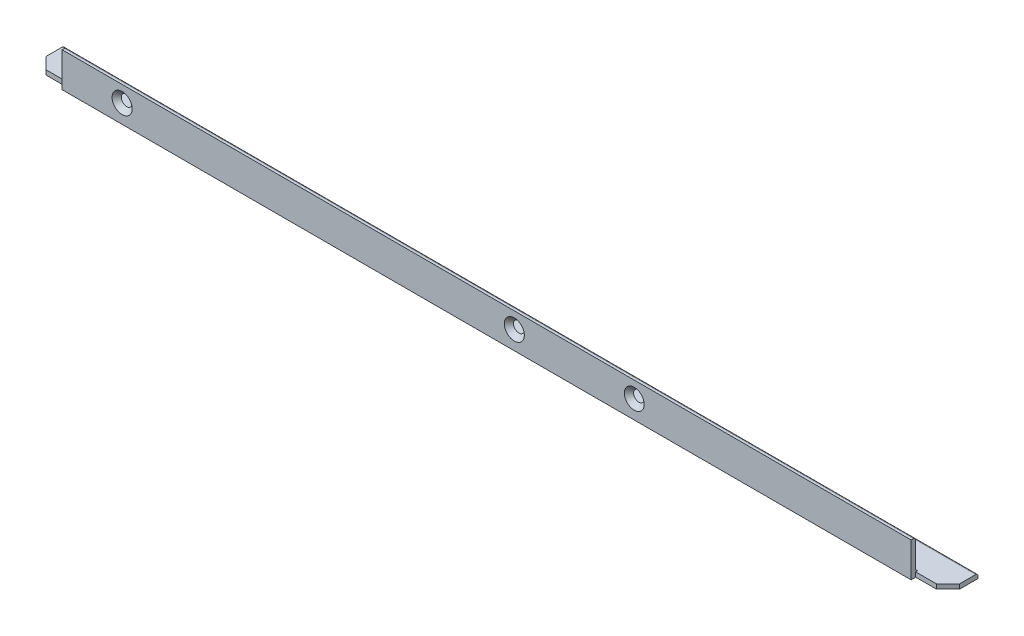
SolidWorks part; units mm, degrees
material "1060 Сплав"
ref_plane "Front" through (0, 0, 0) normal (0, 0, 1) x (1, 0, 0)
ref_plane "Top" through (0, 0, 0) normal (0, 1, 0) x (1, 0, 0)
ref_plane "Right" through (0, 0, 0) normal (1, 0, 0) x (0, 0, -1)
sketch "Эскиз1" plane through (0, 0, 0) normal (1, 0, 0) x (0, 0, -1)
  line L0 (0, 0) -> (0, 15)
  line L1 (0, 0) -> (15, 0)
  line L2 (0, 15) -> (1, 15)
  line L3 (2, 14) -> (2, 3)
  line L4 (3, 2) -> (14, 2)
  line L5 (15, 1) -> (15, 0)
  arc A0 (14, 2) -> (15, 1) centre (14, 1) cw
  arc A1 (1, 15) -> (2, 14) centre (1, 14) cw
  arc A2 (2, 3) -> (3, 2) centre (3, 3) ccw
  point P9 (15, 2)
  point P12 (2, 15)
  dimension "D5" = 1
  dimension "D1" = 15
  dimension "D2" = 15
  dimension "D3" = 2
  dimension "D4" = 2
extrude "Бобышка-Вытянуть1" add sketch "Эскиз1" along normal blind 396
sketch "Эскиз4" plane through (0, 0, 0) normal (0, -1, 0) x (1, 0, 0)
  line L0 (396, -15) -> (0, -15) construction
  line L1 (0, 0) -> (0, -15) construction
  line L2 (396, 0) -> (396, -15) construction
  circle A0 centre (371, -8) radius 2.25
  circle A1 centre (198, -8) radius 2.25
  circle A2 centre (25, -8) radius 2.25
  dimension "D1" = 4.5
  dimension "D2" = 7
  dimension "D3" = 25
  dimension "D4" = 4.5
  dimension "D5" = 25
  dimension "D6" = 7
  dimension "D7" = 173
  dimension "D8" = 4.5
extrude "Вырез-Вытянуть3" cut sketch "Эскиз4" against normal blind 2
chamfer "Фаска1" distance 2.05 angle 45 3 edges at (25, 0, -10.25) (371, 0, -10.25) (198, 0, -10.25)
sketch "Эскиз5" [suppressed] plane through (0, 2, 0) normal (0, 1, 0) x (1, 0, 0)
  line L0 (432, 14) -> (432, 3) construction
  line L1 (432, 15) -> (0, 15) construction
  line L2 (0, 14) -> (0, 3) construction
  circle A0 centre (392, 8) radius 2.3
  circle A1 centre (40, 8) radius 2.3
  dimension "D1" = 4.6
  dimension "D2" = 40
  dimension "D3" = 7
  dimension "D4" = 4.6
  dimension "D5" = 7
  dimension "D6" = 40
extrude "Вырез-Вытянуть4" [suppressed] cut sketch "Эскиз5" against normal through all
chamfer "Фаска3" [suppressed] distance 2.05 angle 45
sketch "Эскиз6" plane through (396, 0, 0) normal (1, 0, 0) x (0, 0, -1)
  line L0 (0, 0) -> (15, 0) construction
  line L1 (0, 15) -> (2, 15)
  line L2 (0, 15) -> (0, 0)
  line L3 (0, 0) -> (2, 0)
  line L4 (2, 0) -> (2, 2)
  line L5 (2, 2) -> (3, 2)
  line L6 (3, 2) -> (3, 15)
  line L7 (3, 15) -> (2, 15)
extrude "Вырез-Вытянуть5" cut sketch "Эскиз6" against normal blind 14
sketch "Эскиз7" plane through (0, 0, 0) normal (-1, 0, 0) x (0, 0, 1)
  line L0 (0, 0) -> (-15, 0) construction
  line L1 (0, 15) -> (-2, 15)
  line L2 (0, 15) -> (0, 0)
  line L3 (0, 0) -> (-2, 0)
  line L4 (-3, 2) -> (-2, 2)
  line L5 (-2, 2) -> (-2, 0)
  line L6 (-3, 2) -> (-3, 15)
  line L7 (-3, 15) -> (-2, 15)
extrude "Вырез-Вытянуть6" cut sketch "Эскиз7" against normal blind 14
sketch "Эскиз9" plane through (0, 2, 0) normal (0, 1, 0) x (1, 0, 0)
  line L0 (0, 2) -> (0, 7)
  line L1 (0, 14) -> (0, 2) construction
  line L2 (0, 7) -> (5, 2)
  line L3 (14, 2) -> (0, 2) construction
  line L4 (5, 2) -> (0, 2)
  line L5 (396, 2) -> (396, 7)
  line L6 (396, 14) -> (396, 2) construction
  line L7 (396, 7) -> (391, 2)
  line L8 (382, 2) -> (396, 2) construction
  line L9 (391, 2) -> (396, 2)
  dimension "D1" = 5
  dimension "D2" = 5
  dimension "D3" = 5
  dimension "D4" = 5
extrude "Вырез-Вытянуть7" cut sketch "Эскиз9" against normal through all
sketch "Эскиз10" plane through (0, 0, -2) normal (0, 0, -1) x (-1, 0, 0)
  line L0 (-382, 15) -> (-14, 15) construction
  line L2 (-14, 3) -> (-14, 14) construction
  circle A1 centre (-134, 8) radius 2.25
  dimension "D1" = 120
  dimension "D5" = 4.5
  dimension "D6" = 7
extrude "Вырез-Вытянуть8" [suppressed] cut sketch "Эскиз10" against normal through all
sketch "Эскиз11" plane through (0, 0, -2) normal (0, 0, -1) x (-1, 0, 0)
  line L0 (-382, 15) -> (-14, 15) construction
  line L2 (-382, 3) -> (-382, 14) construction
  circle A1 centre (-262, 8) radius 2.25
  dimension "D1" = 120
  dimension "D2" = 4.5
  dimension "D4" = 7
extrude "Вырез-Вытянуть9" cut sketch "Эскиз11" against normal through all
sketch "Эскиз12" [suppressed] plane through (0, 0, -2) normal (0, 0, -1) x (-1, 0, 0)
  line L0 (-382, 15) -> (-14, 15) construction
  line L1 (-382, 15) -> (-14, 15) construction
  line L2 (-382, 3) -> (-382, 14) construction
  circle A0 centre (-242, 8) radius 2.3
  circle A1 centre (-332, 8) radius 2.3
  dimension "D1" = 4.6
  dimension "D2" = 4.6
  dimension "D3" = 7
  dimension "D4" = 7
  dimension "D5" = 26
  dimension "D6" = 170
extrude "Вырез-Вытянуть10" [suppressed] cut sketch "Эскиз12" against normal through all
chamfer "Фаска4" [suppressed] distance 2.05 angle 45
sketch "Эскиз13" plane through (0, 0, -2) normal (0, 0, -1) x (-1, 0, 0)
  line L0 (-382, 15) -> (-14, 15) construction
  circle A0 centre (-40, 8) radius 2.3
  circle A1 centre (-210, 8) radius 2.3
  dimension "D1" = 4.6
  dimension "D2" = 7
  dimension "D3" = 40
  dimension "D5" = 170
  dimension "D4" = 2
extrude "Вырез-Вытянуть11" cut sketch "Эскиз13" against normal through all
chamfer "Фаска5" distance 2.05 angle 45 3 edges at (262, 10.25, 0) (40, 10.3, 0) (210, 10.3, 0)
